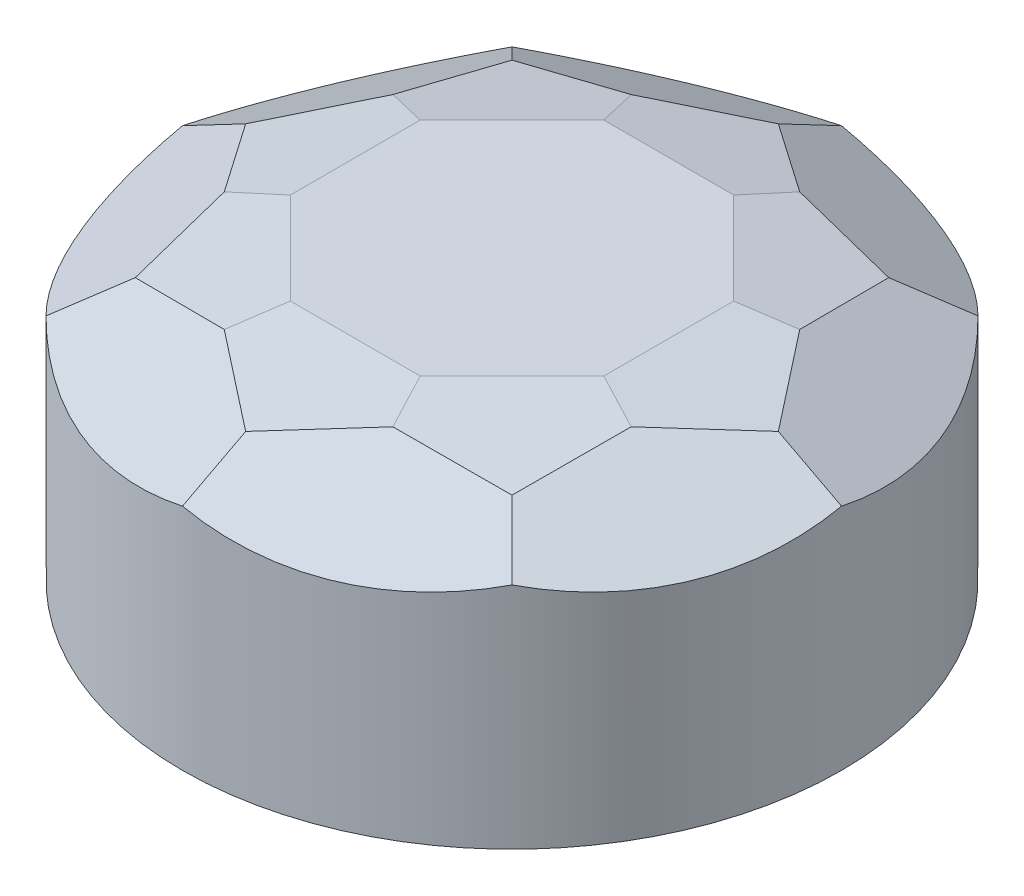
SolidWorks part; units mm, degrees
ref_plane "Front Plane" through (0, 0, 0) normal (0, 0, 1) x (1, 0, 0)
ref_plane "Top Plane" through (0, 0, 0) normal (0, 1, 0) x (1, 0, 0)
ref_plane "Right Plane" through (0, 0, 0) normal (1, 0, 0) x (0, 0, -1)
sketch "Sketch1" plane through (0, 0, 0) normal (0, 1, 0) x (1, 0, 0)
  circle A0 centre (0, 0) radius 3.25
  dimension "D1" = 6.5
extrude "Boss-Extrude1" add sketch "Sketch1" along normal blind 4
sketch "Sketch2" plane through (0, 4, 0) normal (0, 1, 0) x (1, 0, 0)
  line L1 (0, 2.5561) -> (-1.8075, 1.8075)
  line L2 (-1.8075, 1.8075) -> (-2.5561, 0)
  line L3 (-2.5561, 0) -> (-1.8075, -1.8075)
  line L4 (-1.8075, -1.8075) -> (0, -2.5561)
  line L5 (0, -2.5561) -> (1.8075, -1.8075)
  line L6 (1.8075, -1.8075) -> (2.5561, 0)
  line L7 (2.5561, 0) -> (1.8075, 1.8075)
  line L8 (1.8075, 1.8075) -> (0, 2.5561)
  circle A0 centre (0, 0) radius 2.3616 construction
extrude "Boss-Extrude2" add sketch "Sketch2" along normal blind 1
chamfer "Chamfer1" distance 0.88 distance2 1 8 edges at (-0.9037, 4, 2.1818) (-2.1818, 4, 0.9037) (-2.1818, 4, -0.9037) (-0.9037, 4, -2.1818) (0.9037, 4, -2.1818) (2.1818, 4, -0.9037) (2.1818, 4, 0.9037) (0.9037, 4, 2.1818) first distance on face at (0, 4, 3.25)
sketch "Sketch3" plane through (0, 5, 0) normal (0, 1, 0) x (1, 0, 0)
  line L1 (-0.6206, 1.4983) -> (-1.4983, 0.6206)
  line L2 (-1.4983, 0.6206) -> (-1.4983, -0.6206)
  line L3 (-1.4983, -0.6206) -> (-0.6206, -1.4983)
  line L4 (-0.6206, -1.4983) -> (0.6206, -1.4983)
  line L5 (0.6206, -1.4983) -> (1.4983, -0.6206)
  line L6 (1.4983, -0.6206) -> (1.4983, 0.6206)
  line L7 (1.4983, 0.6206) -> (0.6206, 1.4983)
  line L8 (0.6206, 1.4983) -> (-0.6206, 1.4983)
  circle A0 centre (0, 0) radius 1.4983 construction
extrude "Boss-Extrude3" add sketch "Sketch3" along normal blind 0.5
chamfer "Chamfer2" distance 1.07 distance2 0.5 8 edges at (-1.0595, 5, 1.0595) (-1.4983, 5, 0) (0, 5, 1.4983) (-1.0595, 5, -1.0595) (0, 5, -1.4983) (1.0595, 5, -1.0595) (1.4983, 5, 0) (1.0595, 5, 1.0595) tangent propagation no first distance on face at (0, 5, 0)
scale "Scale1" scale about origin uniform scaling no x scale factor 1 y scale factor 0.5 z scale factor 1
sketch "Sketch4" plane through (0, 0, 0) normal (0, -1, 0) x (1, 0, 0)
  circle A0 centre (0, 0) radius 3.15
  circle A1 centre (0, 0) radius 3.45
  dimension "D3" = 6.3
extrude "Cut-Extrude1" cut sketch "Sketch4" against normal through all
equation "\"clearance\"= 0.3mm ' Freely and easily sliding. Used as a gap between the telescopic sections."
equation "\"clearance2\" = 0.1mm ' Used as a gap between rings next to each other."
equation "\"interference\"= 0.1mm ' This is like clearance1 but when two parts should just fit together rather than freely spin."
equation "\"D3@Sketch4\"=6.50mm - \"interference\" * 2"
